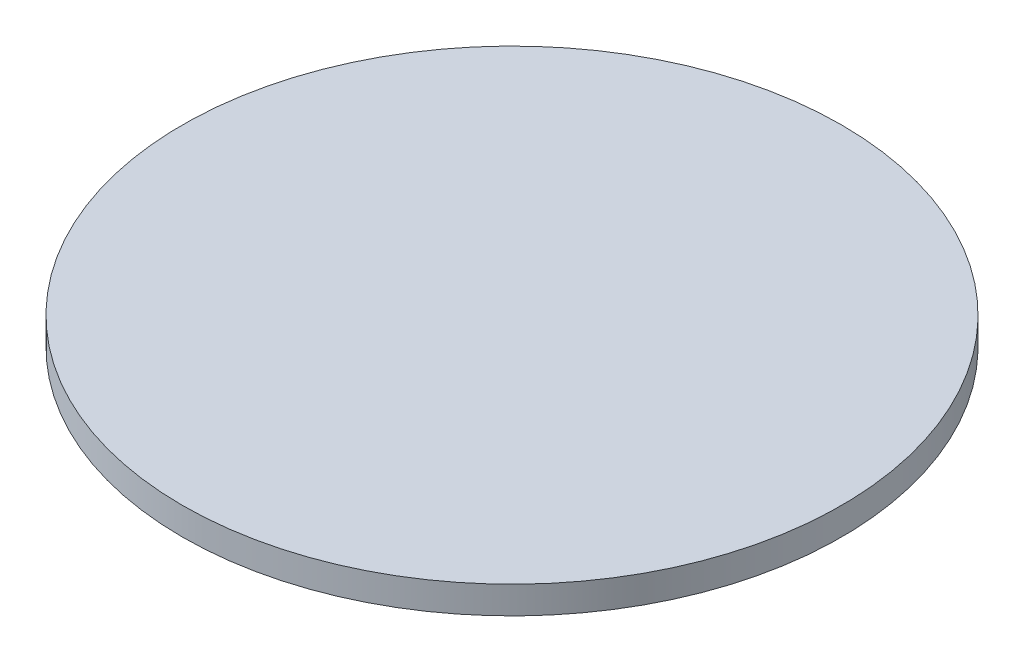
SolidWorks part; units mm, degrees
ref_plane "Front Plane" through (0, 0, 0) normal (0, 0, 1) x (1, 0, 0)
ref_plane "Top Plane" through (0, 0, 0) normal (0, 1, 0) x (1, 0, 0)
ref_plane "Right Plane" through (0, 0, 0) normal (1, 0, 0) x (0, 0, -1)
sketch "Sketch1" plane through (0, 0, 0) normal (0, 1, 0) x (1, 0, 0)
  circle A0 centre (0, 0) radius 60
  dimension "D1" = 120
extrude "Boss-Extrude1" add sketch "Sketch1" along normal blind 5
ref_axis "Axis1" through (0, 0, 0) along (0, -1, 0)
sketch "Sketch2" plane through (0, 5, 0) normal (0, 1, 0) x (1, 0, 0)
  line L0 (0, 0) -> (60, 0)
  line L1 (0, 0) -> (0, 60)
  circle A0 centre (0, 0) radius 60 construction
